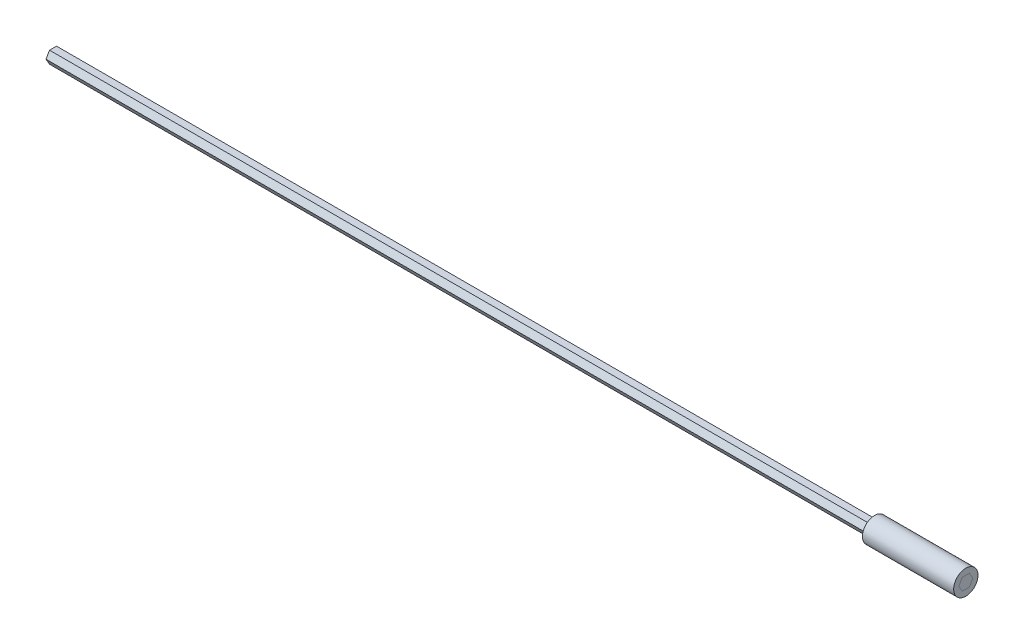
SolidWorks part; units mm, degrees
ref_plane "Front Plane" through (0, 0, 0) normal (0, 0, 1) x (1, 0, 0)
ref_plane "Top Plane" through (0, 0, 0) normal (0, 1, 0) x (1, 0, 0)
ref_plane "Right Plane" through (0, 0, 0) normal (1, 0, 0) x (0, 0, -1)
sketch "Sketch1" plane through (0, 0, 0) normal (1, 0, 0) x (0, 0, -1)
  line L1 (1.1547, 0) -> (0.5774, 1)
  line L2 (0.5774, 1) -> (-0.5774, 1)
  line L3 (-0.5774, 1) -> (-1.1547, 0)
  line L4 (-1.1547, 0) -> (-0.5774, -1)
  line L5 (-0.5774, -1) -> (0.5774, -1)
  line L6 (0.5774, -1) -> (1.1547, 0)
  circle A1 centre (0, 0) radius 1 construction
  dimension "D1" = 2
extrude "Axle-Hex-2mm" add sketch "Sketch1" along normal mid plane 150
ref_axis "Axis1" through (-70.3214, 0, 0) along (1, 0, 0)
sketch "Sketch2" plane through (75, 0, 0) normal (1, 0, 0) x (0, 0, -1)
  line L12 (0.5774, -1) -> (1.1547, 0)
  line L13 (1.1547, 0) -> (0.5774, 1)
  line L14 (0.5774, 1) -> (-0.5774, 1)
  line L15 (-0.5774, 1) -> (-1.1547, 0)
  line L16 (-1.1547, 0) -> (-0.5774, -1)
  line L17 (-0.5774, -1) -> (0.5774, -1)
  line L18 (0.5774, -1) -> (1.1547, 0)
  line L19 (1.1547, 0) -> (0.5774, 1)
  line L20 (0.5774, 1) -> (-0.5774, 1)
  line L21 (-0.5774, 1) -> (-1.1547, 0)
  line L22 (-1.1547, 0) -> (-0.5774, -1)
  line L23 (-0.5774, -1) -> (0.5774, -1)
  circle A0 centre (0, 0) radius 2
  dimension "D2" = 4
  dimension "D1" = 0
extrude "Boss-Extrude1" add sketch "Sketch2" against normal blind 15 separate body
